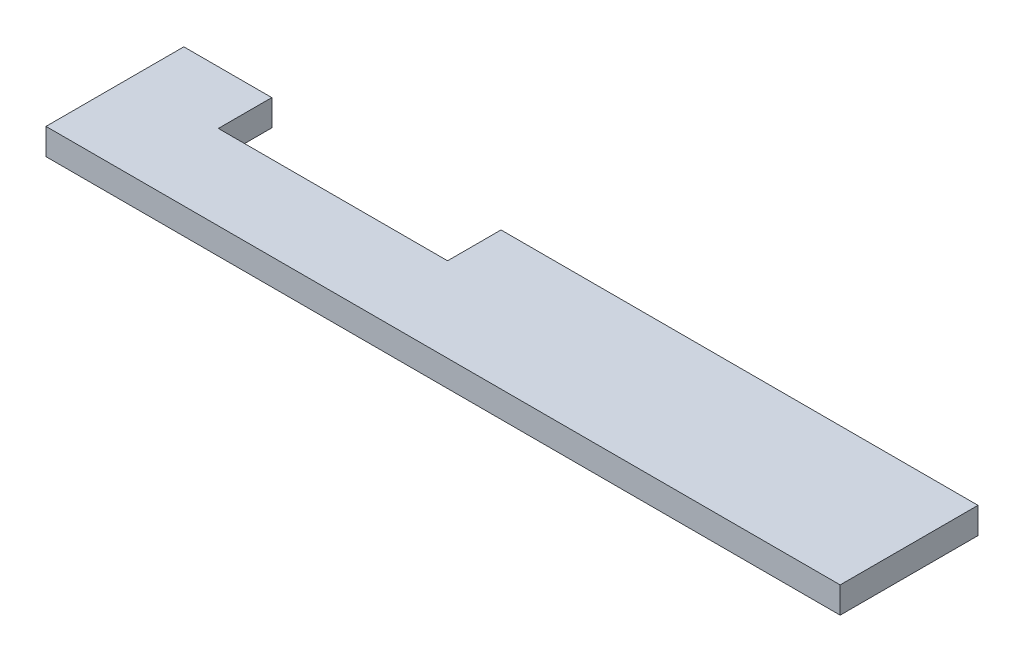
SolidWorks part; units mm, degrees
ref_plane "Front Plane" through (0, 0, 0) normal (0, 0, 1) x (1, 0, 0)
ref_plane "Top Plane" through (0, 0, 0) normal (0, 1, 0) x (1, 0, 0)
ref_plane "Right Plane" through (0, 0, 0) normal (1, 0, 0) x (0, 0, -1)
sketch "Sketch1" plane through (0, 0, 0) normal (0, 1, 0) x (1, 0, 0)
  line L1 (-60.5, -10.5) -> (60.5, -10.5)
  line L2 (-60.5, -10.5) -> (-60.5, 10.5)
  line L3 (-60.5, 10.5) -> (60.5, 10.5)
  line L4 (60.5, -10.5) -> (60.5, 10.5)
  line L5 (-60.5, -10.5) -> (60.5, 10.5) construction
  line L6 (-60.5, 10.5) -> (60.5, -10.5) construction
  point P0 (0, 0)
  dimension "D1" = 121
  dimension "D2" = 21
extrude "Boss-Extrude1" add sketch "Sketch1" along normal blind 4
sketch "Sketch2" plane through (0, 0, 0) normal (0, 1, 0) x (1, 0, 0)
  line L0 (60.5, 10.5) -> (-60.5, 10.5) construction
  line L1 (-47.0996, 10.5) -> (-12.1741, 10.5)
  line L2 (-47.0996, 10.5) -> (-47.0996, 2.3572)
  line L3 (-47.0996, 2.3572) -> (-12.1741, 2.3572)
  line L4 (-12.1741, 10.5) -> (-12.1741, 2.3572)
extrude "Cut-Extrude1" cut sketch "Sketch2" along normal through all both
